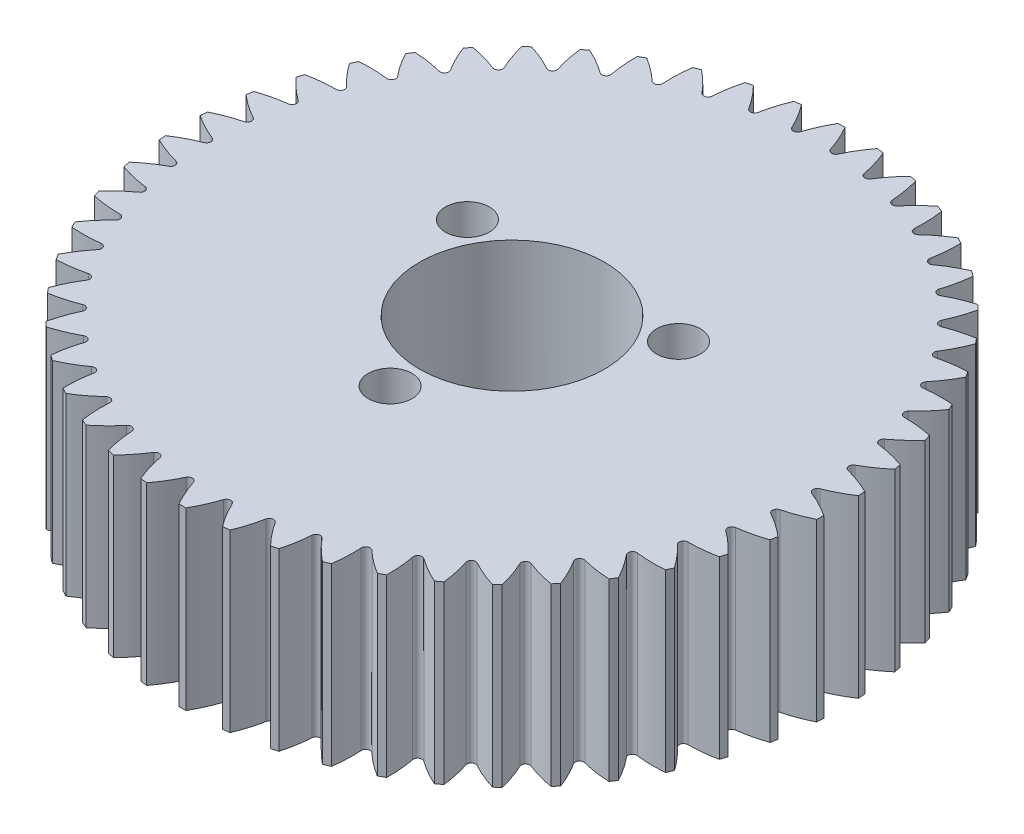
SolidWorks part; units mm, degrees
ref_plane "Front Plane" through (0, 0, 0) normal (0, 0, 1) x (1, 0, 0)
ref_plane "Top Plane" through (0, 0, 0) normal (0, 1, 0) x (1, 0, 0)
ref_plane "Right Plane" through (0, 0, 0) normal (1, 0, 0) x (0, 0, -1)
ref_plane "Plane1" through (0, 0, 0) normal (0, 0, -1) x (-1, 0, 0)
sketch "Sketch1" plane through (0, 0, 0) normal (0, 0, -1) x (-1, 0, 0)
  line L0 (-33.8, -18) -> (0, -18)
  line L1 (0, -18) -> (0, 0)
  line L2 (0, 0) -> (-33.8, 0)
  line L3 (-33.8, 0) -> (-33.8, -18)
  line L4 (0, -18) -> (0, 0) construction
revolve "Revolve1" add sketch "Sketch1" angle 360 about L4 reverse direction yes
sketch "Sketch2" plane through (0, 0, 0) normal (0, 1, 0) x (-1, 0, 0)
  arc A0 (-32.2526, 10.1098) -> (-33.1336, 6.6785) centre (0, 0) ccw
  arc A1 (-30.2823, 7.3484) -> (-33.1336, 6.6785) centre (-28.503, -6.6293) ccw
  arc A2 (-30.2823, 7.3484) -> (-30.0767, 8.1492) centre (-30.3343, 7.7885) ccw
  arc A3 (-30.0767, 8.1492) -> (-32.2526, 10.1098) centre (-21.7837, 19.5407) cw
extrude "Cut-Extrude1" cut sketch "Sketch2" against normal through all
pattern_circular "CirPattern1" count 50 over 360 about axis through (0, -18, 0) along (0, 1, 0) of "Cut-Extrude1"
hole_wizard "CBORE for M4 Hex Head Machine Screw1" positions "Sketch53" profile "Sketch52" counterbore size "M4" standard "ANSI Metric"
sketch "Sketch53" plane through (0, -18, 0) normal (0, -1, 0) x (-1, 0, 0)
  point P0 (0, -12.5)
  point P1 (10.8253, 6.25)
  point P2 (-10.8253, 6.25)
sketch "Sketch52" plane through (0, -18, 12.5) normal (1, 0, 0) x (0, 0, -1)
  line L0 (0, 0) -> (0, 18)
  line L1 (0, 18) -> (2.25, 18)
  line L3 (2.25, 18) -> (2.25, 4)
  line L4 (2.25, 4) -> (4.125, 4)
  line L5 (4.125, 4) -> (4.125, 0)
  line L7 (4.125, 0) -> (0, 0)
  line L11 (0, -6.35) -> (0, 107.95) construction
  dimension "Thru Hole Dia." = 4.5
  dimension "Thru Hole Depth" = 18
  dimension "C'Bore Dia." = 8.25
  dimension "C'Bore Depth" = 4
hole_wizard "Ø19.0 (19) Diameter Hole1" positions "Sketch55" profile "Sketch54" hole size "Ø19.0" standard "ANSI Metric"
sketch "Sketch55" plane through (0, 0, 0) normal (0, 1, 0) x (1, 0, 0)
  point P0 (0, 0)
sketch "Sketch54" plane through (0, 0, 0) normal (1, 0, 0) x (0, 0, 1)
  line L0 (0, 0) -> (0, 18)
  line L1 (0, 18) -> (9.5, 18)
  line L2 (9.5, 18) -> (9.5, 0)
  line L5 (9.5, 0) -> (0, 0)
  line L11 (0, -6.35) -> (0, 107.95) construction
  dimension "Thru Hole Dia." = 19
  dimension "Thru Hole Depth" = 18
fillet "Fillet1" radius 3 6 edges at (-2.4473, -16, 9.1794) (-9.1732, -16, -2.4703) (-6.7259, -16, -6.7091) (9.1732, -16, -2.4703) (6.7259, -16, -6.7091) (2.4473, -16, 9.1794) tangent propagation no
